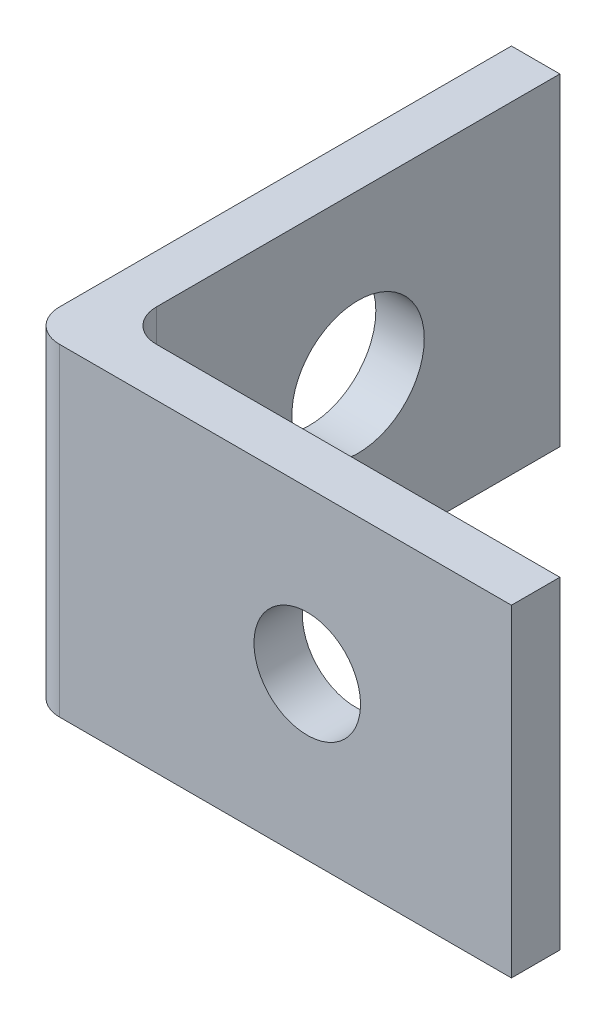
SolidWorks part; units mm, degrees
ref_plane "Спереди" through (0, 0, 0) normal (0, 0, 1) x (1, 0, 0)
ref_plane "Сверху" through (0, 0, 0) normal (0, 1, 0) x (1, 0, 0)
ref_plane "Справа" through (0, 0, 0) normal (1, 0, 0) x (0, 0, -1)
sketch "Эскиз1" plane through (0, 0, 0) normal (0, 1, 0) x (1, 0, 0)
  line L0 (0, 1) -> (0, 15)
  line L5 (0, 15) -> (1.5, 15)
  line L6 (1, 0) -> (15, 0)
  line L7 (15, 0) -> (15, 1.5)
  line L8 (15, 1.5) -> (2.5, 1.5)
  line L9 (1.5, 2.5) -> (1.5, 15)
  arc A0 (1, 0) -> (0, 1) centre (1, 1) cw
  arc A1 (2.5, 1.5) -> (1.5, 2.5) centre (2.5, 2.5) cw
  point P0 (0, 0)
  point P10 (0, 0)
  dimension "D5" = 1
  dimension "D1" = 15
  dimension "D2" = 1.5
  dimension "D3" = 15
  dimension "D4" = 1.5
extrude "Бобышка-Вытянуть1" add sketch "Эскиз1" along normal blind 10
sketch "Эскиз2" plane through (0, 0, 0) normal (0, 0, 1) x (1, 0, 0)
  line L0 (8.25, 0) -> (8.25, 11.3489) construction
  line L3 (1, 0) -> (15, 0) construction
  line L4 (15, 10) -> (15, 0) construction
  point P6 (7.5, 11.3489)
  dimension "D1" = 6.75
sketch "Эскиз3" plane through (0, 0, 0) normal (-1, 0, 0) x (0, 0, 1)
  line L0 (-8.25, 0) -> (-8.25, 11.1434) construction
  line L1 (-15, 0) -> (-1, 0) construction
  dimension "D1" = 6.75
extrude "Вырез-Вытянуть3" cut sketch "Эскиз6" against normal blind 8 contours L4 A0 | A0 L4 region at (7.9754, 5.0104, -1.5) region at (9.3758, 4.9896, -1.5)
sketch "Эскиз6" plane through (-307.9408, -349.2045, -1.5) normal (0, 0, -1) x (-0.9999, 0.0149, 0)
  line L2 (-317.5586, 363.9713) -> (-305.06, 363.7853)
  line L3 (-317.7074, 353.9725) -> (-305.2088, 353.7864)
  line L4 (-311.3093, 363.8783) -> (-311.3093, 353.8772) construction
  circle A0 centre (-311.3093, 358.8778) radius 1.65
sketch "Эскиз12" plane through (1.5, 0, 0) normal (1, 0, 0) x (0, 0, -1)
  line L0 (8.75, 10) -> (8.75, 0) construction
  line L4 (2.5, 0) -> (15, 0)
  line L5 (15, 0) -> (15, 10)
  line L6 (15, 10) -> (2.5, 10)
  line L7 (2.5, 10) -> (2.5, 0)
  line L8 (2.5, 0) -> (15, 0) construction
  line L9 (15, 0) -> (15, 10) construction
  line L10 (15, 10) -> (2.5, 10) construction
  line L11 (2.5, 10) -> (2.5, 0) construction
  circle A0 centre (8.75, 5) radius 2.05
  dimension "D1" = 0
extrude "Вырез-Вытянуть5" cut sketch "Эскиз12" against normal blind 95
